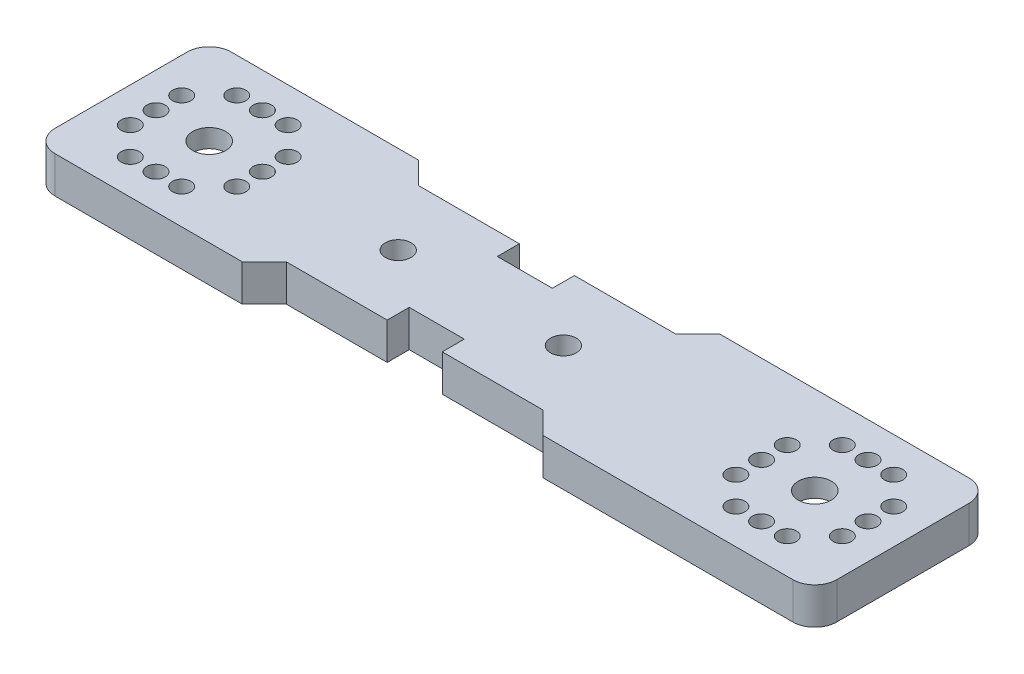
SolidWorks part; units mm, degrees
ref_plane "Front Plane" through (0, 0, 0) normal (0, 0, 1) x (1, 0, 0)
ref_plane "Top Plane" through (0, 0, 0) normal (0, 1, 0) x (1, 0, 0)
ref_plane "Right Plane" through (0, 0, 0) normal (1, 0, 0) x (0, 0, -1)
sketch "Sketch1" plane through (0, 0, 0) normal (0, 1, 0) x (1, 0, 0)
  line L1 (0, 12) -> (57.5, 12)
  line L2 (57.5, 12) -> (57.5, -12)
  line L3 (57.5, -12) -> (0, -12)
  line L4 (0, 12) -> (-49, 12)
  line L5 (-49, 12) -> (-49, -12)
  line L6 (-49, -12) -> (0, -12)
  line L7 (0, 12) -> (0, -12) construction
  point P5 (0, 0)
  dimension "D1" = 24
  dimension "D2" = 57.5
  dimension "D3" = 49
extrude "Boss-Extrude1" add sketch "Sketch1" along normal blind 5
sketch "Sketch2" plane through (0, 0, 0) normal (0, -1, 0) x (1, 0, 0)
  line L0 (57.5, 12) -> (57.5, -12) construction
  line L2 (-49, -12) -> (-49, 12) construction
  circle A0 centre (45.5, 0) radius 10.5
  circle A1 centre (-37, 0) radius 10.5
  point P7 (57.5, 0)
  dimension "D1" = 21
  dimension "D2" = 12
  dimension "D3" = 12
extrude "Cut-Extrude1" cut sketch "Sketch2" against normal blind 2.5
sketch "Sketch3" plane through (0, 2.5, 0) normal (0, -1, 0) x (1, 0, 0)
  circle A0 centre (45.5, 0) radius 2.25
  circle A1 centre (45.5, 7.25) radius 1.25
  circle A2 centre (42, 7.25) radius 1.25
  circle A3 centre (49, 7.25) radius 1.25
  circle A13 centre (52.75, 0) radius 1.25
  circle A14 centre (52.75, -3.5) radius 1.25
  circle A15 centre (52.75, 3.5) radius 1.25
  circle A16 centre (45.5, -7.25) radius 1.25
  circle A17 centre (42, -7.25) radius 1.25
  circle A18 centre (49, -7.25) radius 1.25
  circle A19 centre (38.25, 0) radius 1.25
  circle A20 centre (38.25, 3.5) radius 1.25
  circle A21 centre (38.25, -3.5) radius 1.25
  circle A22 centre (45.5, 0) radius 10.5 construction
  circle A36 centre (-37, 0) radius 2.25
  circle A37 centre (-37, 7.25) radius 1.25
  circle A38 centre (-40.5, 7.25) radius 1.25
  circle A39 centre (-33.5, 7.25) radius 1.25
  circle A49 centre (-37, 0) radius 10.5 construction
  circle A50 centre (-29.75, 3.5) radius 1.25
  circle A51 centre (-29.75, 0) radius 1.25
  circle A52 centre (-29.75, -3.5) radius 1.25
  circle A53 centre (-33.5, -7.25) radius 1.25
  circle A54 centre (-37, -7.25) radius 1.25
  circle A55 centre (-40.5, -7.25) radius 1.25
  circle A56 centre (-44.25, -3.5) radius 1.25
  circle A57 centre (-44.25, 0) radius 1.25
  circle A58 centre (-44.25, 3.5) radius 1.25
  dimension "D1" = 4.5
  dimension "D2" = 2.5
  dimension "D7" = 2.5
  dimension "D3" = 7.25
  dimension "D4" = 3.5
  dimension "D5" = 3.5
  dimension "D8" = 7.25
  dimension "D9" = 3.5
  dimension "D10" = 3.5
  dimension "D6" = 4
  dimension "D11" = 4
extrude "Cut-Extrude2" cut sketch "Sketch3" against normal through all
sketch "Sketch7" plane through (0, 0, 0) normal (0, -1, 0) x (1, 0, 0)
  line L0 (-17.5, 12) -> (17.5, 12)
  line L1 (-49, 12) -> (57.5, 12) construction
  line L2 (17.5, 12) -> (17.5, 9)
  line L3 (17.5, 9) -> (-17.5, 9)
  line L4 (-17.5, 9) -> (-17.5, 12)
  line L5 (55, 0) -> (-55, 0) construction
  line L6 (17.5, -9) -> (-17.5, -9)
  line L7 (17.5, -12) -> (17.5, -9)
  line L8 (-17.5, -12) -> (17.5, -12)
  line L9 (-17.5, -9) -> (-17.5, -12)
  point P6 (0, 9)
  dimension "D1" = 3
  dimension "D2" = 35
extrude "Cut-Extrude4" cut sketch "Sketch7" against normal through all
sketch "Sketch6" plane through (0, 0, 0) normal (0, -1, 0) x (1, 0, 0)
  line L0 (-3.75, 9) -> (3.75, 9)
  line L1 (17.5, 12) -> (57.5, 12) construction
  line L2 (3.75, 9) -> (3.75, 6)
  line L3 (3.75, 6) -> (-3.75, 6)
  line L4 (-3.75, 6) -> (-3.75, 9)
  line L5 (55, 0) -> (-55, 0) construction
  line L6 (3.75, -6) -> (-3.75, -6)
  line L7 (3.75, -9) -> (3.75, -6)
  line L8 (-3.75, -9) -> (3.75, -9)
  line L9 (-3.75, -6) -> (-3.75, -9)
  line L10 (-17.5, 9) -> (17.5, 9) construction
  point P4 (37.5, 12)
  point P14 (37.5, -12)
  point P16 (0, 9)
  point P17 (0, 9)
  dimension "D1" = 3
  dimension "D2" = 7.5
extrude "Cut-Extrude3" cut sketch "Sketch6" against normal through all
sketch "Sketch8" plane through (0, 5, 0) normal (0, 1, 0) x (1, 0, 0)
  line L0 (-49, 0) -> (57.5, 0) construction
  line L1 (3.75, 9) -> (3.75, 6) construction
  line L2 (57.5, -12) -> (57.5, 12) construction
  line L3 (0, -2.75) -> (0, 2.75) construction
  line L4 (-49, 12) -> (-49, -12) construction
  circle A3 centre (11.25, 0) radius 1.75
  circle A6 centre (-11.25, 0) radius 1.75
  dimension "D1" = 7.5
  dimension "D2" = 3.5
extrude "Cut-Extrude5" cut sketch "Sketch8" against normal through all
fillet "Fillet3" radius 3 4 edges at (57.5, 2.5, 12) (57.5, 2.5, -12) (-49, 2.5, -12) (-49, 2.5, 12)
chamfer "Chamfer1" distance 3 angle 45 4 edges at (17.5, 2.5, -12) (-17.5, 2.5, -12) (17.5, 2.5, 12) (-17.5, 2.5, 12)
